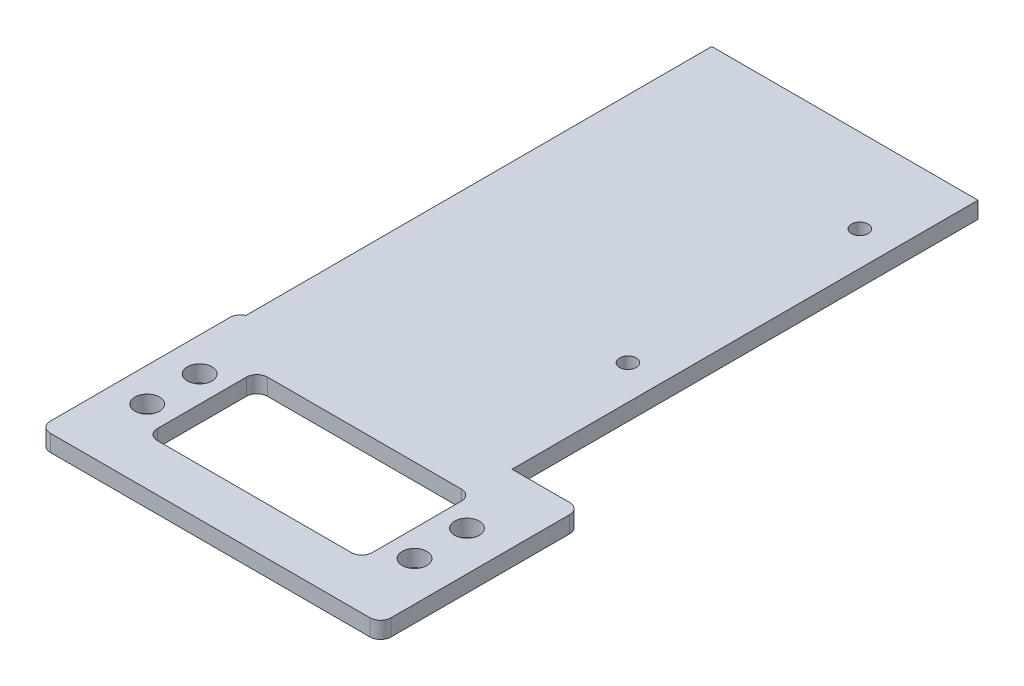
SolidWorks part; units mm, degrees
ref_plane "Front Plane" through (0, 0, 0) normal (0, 0, 1) x (1, 0, 0)
ref_plane "Top Plane" through (0, 0, 0) normal (0, 1, 0) x (1, 0, 0)
ref_plane "Right Plane" through (0, 0, 0) normal (1, 0, 0) x (0, 0, -1)
sketch "Sketch1" plane through (0, 0, 0) normal (0, 1, 0) x (1, 0, 0)
  line L0 (-31.3, 19.05) -> (-32.5, 19.05)
  line L1 (32.5, -19.05) -> (-32.5, -19.05)
  line L2 (32.5, -19.05) -> (32.5, 19.05)
  line L3 (32.5, 19.05) -> (19.5, 19.05)
  line L4 (-32.5, -19.05) -> (-32.5, 19.05)
  line L5 (32.5, -19.05) -> (-32.5, 19.05) construction
  line L6 (32.5, 19.05) -> (-32.5, -19.05) construction
  line L8 (-31.3, 19.05) -> (-31.3, 107.95)
  line L9 (-31.3, 107.95) -> (19.5, 107.95)
  line L10 (19.5, 19.05) -> (19.5, 107.95)
  point P0 (0, 0)
  point P10 (0, 0)
  dimension "D1" = 65
  dimension "D2" = 38.1
  dimension "D4" = 50.8
  dimension "D5" = 88.9
  dimension "D3" = 13
extrude "Boss-Extrude1" add sketch "Sketch1" along normal blind 3.175
sketch "Sketch2" plane through (0, 3.175, 0) normal (0, 1, 0) x (1, 0, 0)
  line L0 (-0.56, -10.0597) -> (-0.56, 10.9403) construction
  line L3 (-26.06, 15.1128) -> (24.44, 15.1128) construction
  line L4 (19.94, -10.0597) -> (-21.06, -10.0597)
  line L5 (19.94, -10.0597) -> (19.94, 10.9403)
  line L6 (19.94, 10.9403) -> (-21.06, 10.9403)
  line L7 (-21.06, -10.0597) -> (-21.06, 10.9403)
  line L8 (19.94, -10.0597) -> (-21.06, 10.9403) construction
  line L9 (19.94, 10.9403) -> (-21.06, -10.0597) construction
  line L10 (-32.5, 0) -> (32.5, 0) construction
  line L11 (-32.5, 19.05) -> (-32.5, -19.05) construction
  line L12 (32.5, -19.05) -> (32.5, 19.05) construction
  line L13 (-26.06, -5) -> (-26.06, 5) construction
  line L14 (-31.3, 33.0186) -> (-10.66, 33.0186) construction
  line L15 (-31.3, 107.95) -> (-31.3, 19.05) construction
  line L16 (-21.06, 8.2878) -> (-10.66, 8.2878) construction
  line L17 (-10.66, 33.0186) -> (-10.66, 8.2878) construction
  circle A0 centre (-26.06, 5) radius 2.35
  circle A4 centre (-26.06, -5) radius 2.35
  circle A5 centre (24.94, -5) radius 2.35
  circle A6 centre (24.94, 5) radius 2.35
  point P6 (0, 0)
  point P23 (-26.06, 0)
  dimension "D4" = 4.7
  dimension "D1" = 41
  dimension "D2" = 50.5
  dimension "D3" = 10
  dimension "D5" = 21
  dimension "D6" = 20.64
  dimension "D7" = 10.4
  dimension "D8" = 5
extrude "Cut-Extrude1" cut sketch "Sketch2" against normal through all
fillet "Fillet1" radius 2 8 edges at (19.94, 1.5875, -10.9403) (19.94, 1.5875, 10.0597) (-21.06, 1.5875, 10.0597) (-21.06, 1.5875, -10.9403) (32.5, 1.5875, -19.05) (32.5, 1.5875, 19.05) (-32.5, 1.5875, 19.05) (-32.5, 1.5875, -19.05)
sketch "Sketch5" plane through (0, 3.175, 0) normal (0, 1, 0) x (1, 0, 0)
  line L0 (12.95, 47.698) -> (12.95, 91.948) construction
  line L1 (-31.3, 107.95) -> (-31.3, 19.05) construction
  line L3 (19.5, 107.95) -> (-31.3, 107.95) construction
  circle A0 centre (12.95, 91.948) radius 1.5875
  circle A1 centre (12.95, 47.698) radius 1.5875
  dimension "D1" = 44.25
  dimension "D2" = 3.175
  dimension "D3" = 44.25
  dimension "D4" = 16.002
extrude "Cut-Extrude2" cut sketch "Sketch5" against normal through all
equation "\"test\"=13"
equation "\"D3@Sketch1\"=\"test\""
